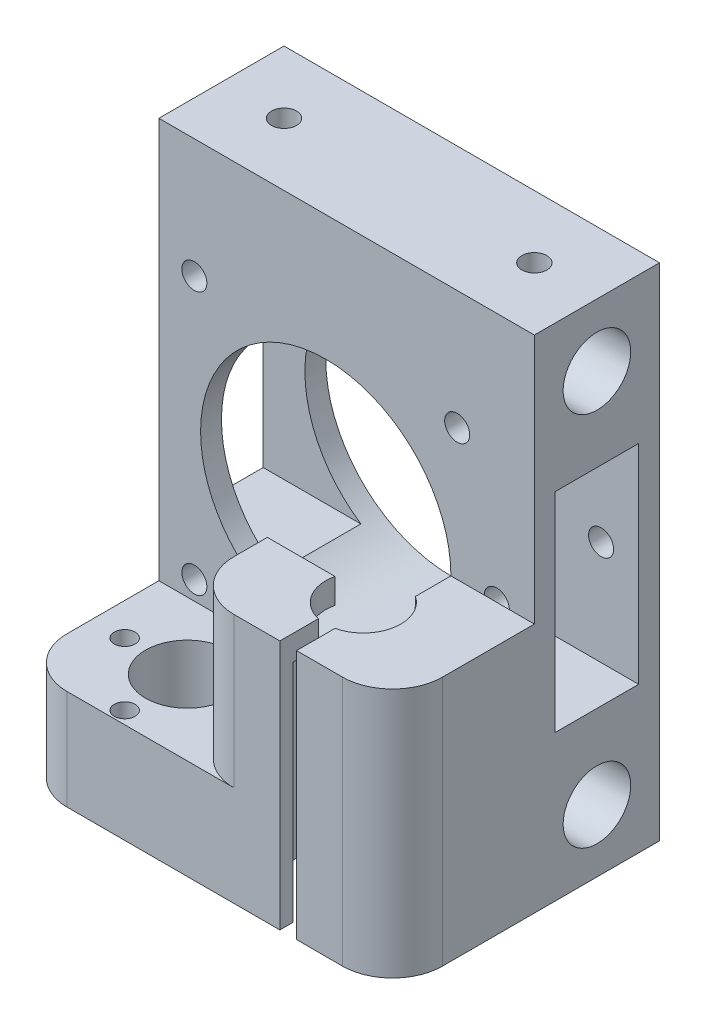
SolidWorks part; units mm, degrees
ref_plane "Front Plane" through (0, 0, 0) normal (0, 0, 1) x (1, 0, 0)
ref_plane "Top Plane" through (0, 0, 0) normal (0, 1, 0) x (1, 0, 0)
ref_plane "Right Plane" through (0, 0, 0) normal (1, 0, 0) x (0, 0, -1)
sketch "Sketch1" plane through (0, 0, 0) normal (0, 0, 1) x (1, 0, 0)
  line L1 (-22.5, -30) -> (22.5, -30)
  line L2 (-22.5, -30) -> (-22.5, 30)
  line L3 (-22.5, 30) -> (22.5, 30)
  line L4 (22.5, -30) -> (22.5, 30)
  line L5 (-22.5, -30) -> (22.5, 30) construction
  line L6 (-22.5, 30) -> (22.5, -30) construction
  point P0 (0, 0)
  dimension "D1" = 45
  dimension "D2" = 60
extrude "Boss-Extrude1" add sketch "Sketch1" along normal blind 15
sketch "Sketch2" plane through (22.5, 0, 0) normal (1, 0, 0) x (0, 0, -1)
  line L0 (-7.5, 30) -> (-7.5, -30) construction
  line L1 (-15, 30) -> (0, 30) construction
  line L2 (-15, -30) -> (0, -30) construction
  line L3 (0, -30) -> (0, 30) construction
  line L4 (-12.5, -12.5) -> (-2.5, -12.5)
  line L5 (-12.5, -12.5) -> (-12.5, 12.5)
  line L6 (-12.5, 12.5) -> (-2.5, 12.5)
  line L7 (-2.5, -12.5) -> (-2.5, 12.5)
  line L8 (-12.5, -12.5) -> (-2.5, 12.5) construction
  line L9 (-12.5, 12.5) -> (-2.5, -12.5) construction
  line L10 (-15, 0) -> (0, 0) construction
  line L11 (-15, -30) -> (-15, 30) construction
  circle A0 centre (-7.5, 22.5) radius 4.05
  circle A1 centre (-7.5, -22.5) radius 4.05
  point P6 (-7.5, 0)
  dimension "D3" = 8.1
  dimension "D1" = 2.5
  dimension "D2" = 25
  dimension "D4" = 22.5
extrude "Cut-Extrude1" cut sketch "Sketch2" against normal through all
sketch "Sketch3" plane through (-22.5, 0, 0) normal (-1, 0, 0) x (0, 0, 1)
  line L1 (15, -30) -> (32, -30)
  line L2 (15, -30) -> (15, -18)
  line L3 (15, -18) -> (32, -18)
  line L4 (32, -30) -> (32, -18)
  dimension "D1" = 17
  dimension "D2" = 12
extrude "Boss-Extrude2" add sketch "Sketch3" against normal up to surface (45 mm away) up to face at (22.5, -22.5, 11.55)
sketch "Sketch4" plane through (0, -18, 0) normal (0, 1, 0) x (1, 0, 0)
  line L0 (22.5, -15) -> (-22.5, -15) construction
  line L1 (22.5, -32) -> (-2.5, -32)
  line L2 (22.5, -32) -> (22.5, -15)
  line L3 (22.5, -15) -> (-2.5, -15)
  line L4 (-2.5, -32) -> (-2.5, -15)
  dimension "D1" = 25
extrude "Boss-Extrude3" add sketch "Sketch4" along normal blind 18
sketch "Sketch5" plane through (0, 0, 32) normal (0, 0, 1) x (1, 0, 0)
  line L0 (10, 0) -> (10, -30) construction
  line L1 (22.5, 0) -> (-2.5, 0) construction
  line L2 (22.5, -30) -> (-22.5, -30) construction
  line L3 (-2.5, 0) -> (22.5, 0) construction
  line L4 (9, -30) -> (11, -30)
  line L5 (9, -30) -> (9, 0)
  line L6 (9, 0) -> (11, 0)
  line L7 (11, -30) -> (11, 0)
  line L8 (9, -30) -> (11, 0) construction
  line L9 (9, 0) -> (11, -30) construction
  point P6 (10, -15)
  dimension "D1" = 2
extrude "Cut-Extrude2" cut sketch "Sketch5" against normal blind 5
sketch "Sketch6" plane through (0, -30, 0) normal (0, -1, 0) x (1, 0, 0)
  line L0 (10, 27) -> (10, 15) construction
  line L1 (11, 27) -> (9, 27) construction
  line L2 (22.5, 15) -> (-2.5, 15) construction
  circle A0 centre (10, 23) radius 4.5
  dimension "D1" = 9
  dimension "D2" = 4
extrude "Cut-Extrude3" cut sketch "Sketch6" against normal through all
sketch "Sketch7" plane through (0, -30, 0) normal (0, -1, 0) x (1, 0, 0)
  line L0 (10, 23) -> (-22.5, 23) construction
  line L1 (-22.5, 32) -> (-22.5, 0) construction
  line L2 (-11.1, 23) -> (-7.5645, 26.5355) construction
  line L3 (-11.1, 23) -> (-11.1, 30.5) construction
  line L4 (-11.1, 23) -> (-7.5645, 19.4645) construction
  circle A0 centre (10, 23) radius 7.5
  circle A1 centre (-11.1, 23) radius 5
  circle A2 centre (-3.6, 23) radius 1.25
  circle A3 centre (-11.1, 30.5) radius 1.25
  circle A4 centre (-11.1, 15.5) radius 1.25
  circle A5 centre (-18.6, 23) radius 1.25
  dimension "D1" = 15
  dimension "D2" = 10
  dimension "D4" = 2.5
  dimension "D8" = 2.5
  dimension "D3" = 21.1
  dimension "D5" = 7.5
  dimension "D6" = 45
  dimension "D7" = 7.5
  dimension "D9" = 45
extrude "Cut-Extrude4" cut sketch "Sketch7" against normal offset from surface (27 mm away) 3 up to face at (10, 0, 25.4859)
sketch "Sketch8" plane through (0, 0, 0) normal (0, 0, -1) x (-1, 0, 0)
  line L0 (2.5, -30) -> (2.5, 30) construction
  line L3 (-22.5, 0) -> (22.5, 0) construction
  line L4 (-22.5, -30) -> (-22.5, 30) construction
  line L5 (22.5, 30) -> (22.5, -30) construction
  line L6 (2.5, 0) -> (18.25, 15.75) construction
  line L7 (22.5, -30) -> (-22.5, -30) construction
  line L8 (-22.5, 30) -> (22.5, 30) construction
  line L9 (-13.25, -15.75) -> (2.5, 0) construction
  line L10 (18.25, -15.75) -> (2.5, 0) construction
  line L11 (2.5, 0) -> (-13.25, 15.75) construction
  circle A0 centre (2.5, 0) radius 15
  circle A1 centre (18.25, 15.75) radius 1.5
  circle A2 centre (-13.25, 15.75) radius 1.5
  circle A3 centre (-13.25, -15.75) radius 1.5
  circle A4 centre (18.25, -15.75) radius 1.5
  dimension "D1" = 30
  dimension "D2" = 3
  dimension "D10" = 3
  dimension "D3" = 0
  dimension "D4" = 45
  dimension "D5" = 31.5
  dimension "D6" = 31.5
  dimension "D7" = 20
  dimension "D8" = 45
  dimension "D9" = 45
extrude "Cut-Extrude5" cut sketch "Sketch8" against normal blind 22
fillet "Fillet1" radius 6 3 edges at (-22.5, -24, 32) (-2.5, -9, 32) (22.5, -15, 32)
sketch "Sketch9" plane through (0, 0, 0) normal (0, 0, -1) x (-1, 0, 0)
  line L0 (-22.5, 0) -> (-12.5, 0) construction
  line L1 (-22.5, -30) -> (-22.5, 30) construction
  circle A0 centre (2.5, 0) radius 15 construction
  circle A1 centre (-18, 0) radius 1.5
  dimension "D1" = 3
  dimension "D2" = 4.5
extrude "Cut-Extrude6" cut sketch "Sketch9" against normal up to surface (15 mm away) up to face at (-19.75, -15.75, 15)
sketch "Sketch10" plane through (0, 30, 0) normal (0, 1, 0) x (1, 0, 0)
  line L0 (-22.5, -7.5) -> (22.5, -7.5) construction
  line L1 (-22.5, -15) -> (-22.5, 0) construction
  line L2 (22.5, -15) -> (22.5, 0) construction
  line L3 (0, -15) -> (0, 0) construction
  line L4 (22.5, -15) -> (-22.5, -15) construction
  circle A0 centre (-15, -7.5) radius 1.5
  circle A1 centre (15, -7.5) radius 1.5
  dimension "D1" = 3
  dimension "D2" = 15
extrude "Cut-Extrude7" cut sketch "Sketch10" against normal blind 5
extrude "Cut-Extrude8" cut sketch "Sketch10<2>" along normal blind 5 from surface starting at face at (-18.6, -30, 24.25)
sketch "Sketch10<2>" plane through (0, 30, 0) normal (0, 1, 0) x (1, 0, 0) same geometry as "Sketch10"
